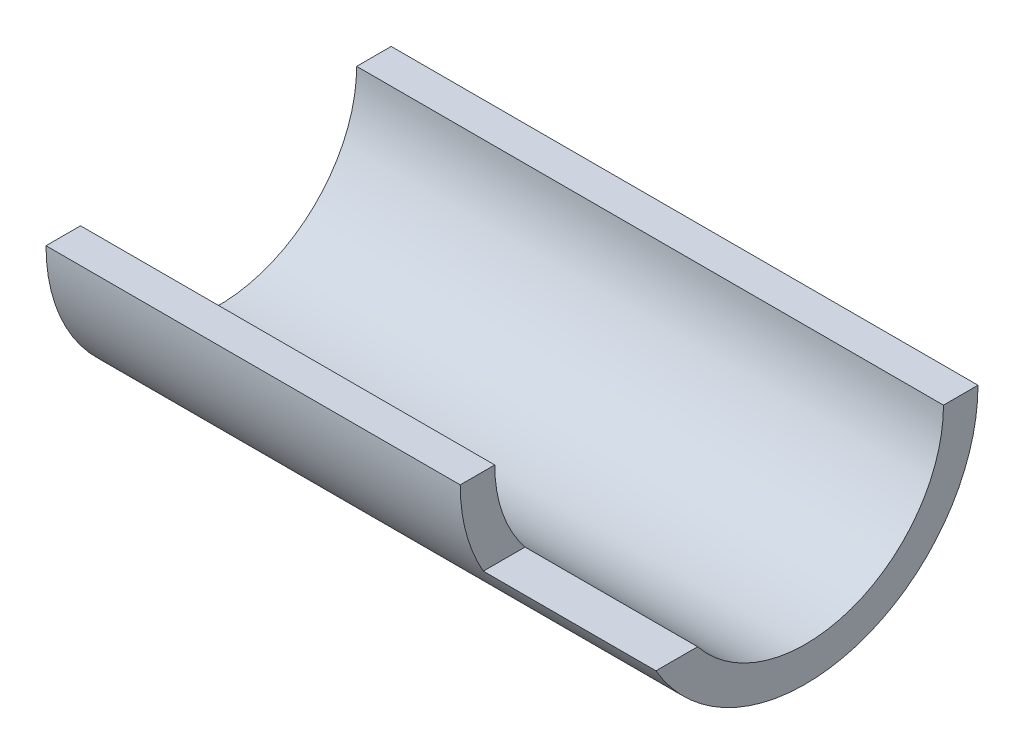
SolidWorks part; units mm, degrees
ref_plane "Front Plane" through (0, 0, 0) normal (0, 0, 1) x (1, 0, 0)
ref_plane "Top Plane" through (0, 0, 0) normal (0, 1, 0) x (1, 0, 0)
ref_plane "Right Plane" through (0, 0, 0) normal (1, 0, 0) x (0, 0, -1)
sketch "Sketch1" plane through (0, 0, 0) normal (1, 0, 0) x (0, 0, -1)
  line L2 (-25.4, 0) -> (-31.75, 0)
  line L3 (31.75, 0) -> (25.4, 0)
  arc A2 (-25.4, 0) -> (25.4, 0) centre (0, 0) ccw
  arc A3 (-31.75, 0) -> (31.75, 0) centre (0, 0) ccw
  dimension "D1" = 31.75
  dimension "D2" = 25.4
  dimension "D3" = 6.35
  dimension "D4" = 6.35
extrude "Boss-Extrude1" add sketch "Sketch1" against normal blind 107.95
sketch "Sketch2" plane through (0, 0, 0) normal (0, 0, 1) x (1, 0, 0)
  line L0 (-107.95, 0) -> (0, 0) construction
  line L1 (-31.75, 0) -> (0, 0)
  line L2 (-31.75, 0) -> (-31.75, -15.875)
  line L3 (-31.75, -15.875) -> (0, -15.875)
  line L4 (0, 0) -> (0, -15.875)
  line L5 (-107.95, 0) -> (-107.95, -31.75) construction
  dimension "D1" = 31.75
  dimension "D2" = 15.875
  dimension "D3" = 76.2
extrude "Cut-Extrude1" cut sketch "Sketch2" along normal blind 127
